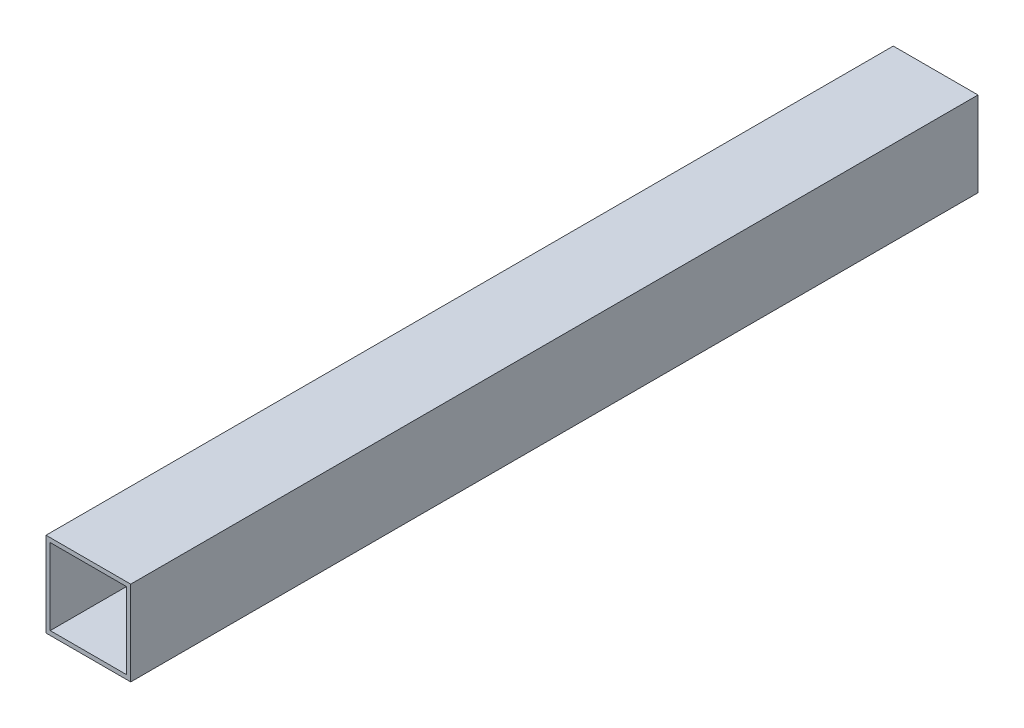
SolidWorks part; units mm, degrees
material "6061-T6 (SS)"
ref_plane "Front" through (0, 0, 0) normal (0, 0, 1) x (1, 0, 0)
ref_plane "Top" through (0, 0, 0) normal (0, 1, 0) x (1, 0, 0)
ref_plane "Right" through (0, 0, 0) normal (1, 0, 0) x (0, 0, -1)
sketch "Sketch1" plane through (0, 0, 0) normal (0, 0, 1) x (1, 0, 0)
  line L0 (-22.5, -22.5) -> (-22.5, 22.5)
  line L1 (-25, -25) -> (25, -25)
  line L2 (-25, -25) -> (-25, 25)
  line L3 (-25, 25) -> (25, 25)
  line L4 (25, -25) -> (25, 25)
  line L5 (-25, -25) -> (25, 25) construction
  line L6 (-25, 25) -> (25, -25) construction
  line L7 (-22.5, 22.5) -> (22.5, 22.5)
  line L8 (22.5, -22.5) -> (22.5, 22.5)
  line L9 (-22.5, -22.5) -> (22.5, -22.5)
  point P0 (0, 0)
  dimension "D2" = 50
  dimension "D1" = 2.5
extrude "Boss-Extrude1" add sketch "Sketch1" along normal mid plane 500
